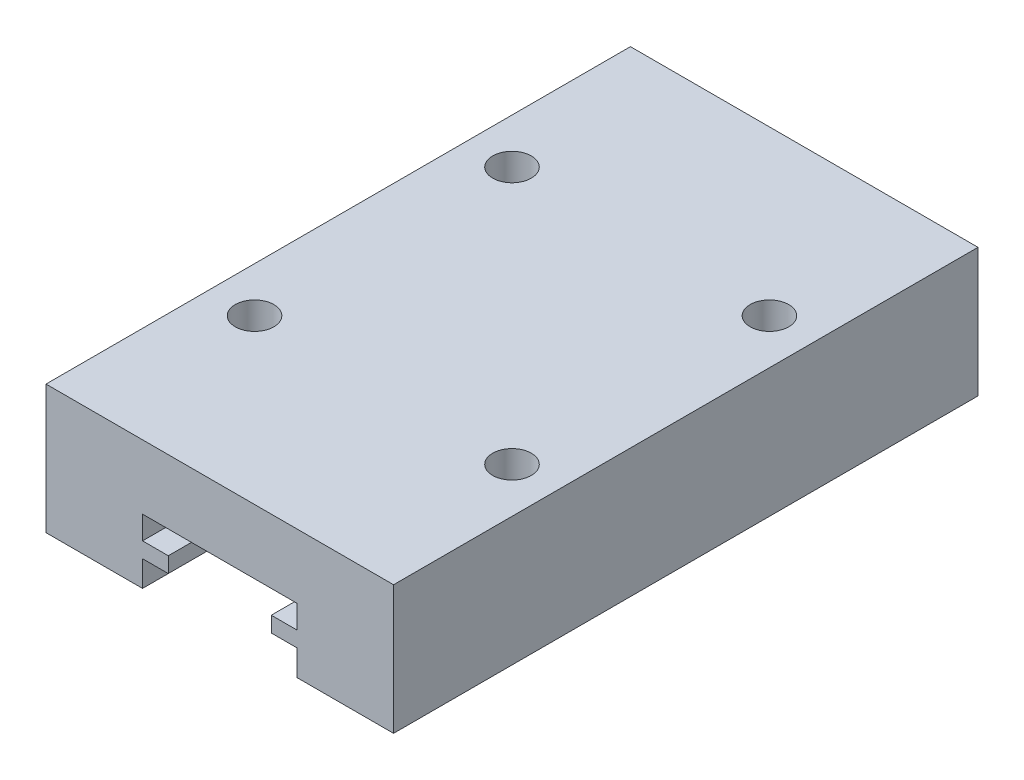
SolidWorks part; units mm, degrees
ref_plane "Plan de face" through (0, 0, 0) normal (0, 0, 1) x (1, 0, 0)
ref_plane "Plan de dessus" through (0, 0, 0) normal (0, 1, 0) x (1, 0, 0)
ref_plane "Plan de droite" through (0, 0, 0) normal (1, 0, 0) x (0, 0, -1)
sketch "Esquisse1" plane through (0, 0, 0) normal (0, 0, 1) x (1, 0, 0)
  line L0 (-22.7955, 10) -> (4.2045, 10)
  line L1 (4.2045, 10) -> (4.2045, 0)
  line L2 (4.2045, 0) -> (-3.2955, 0)
  line L3 (-3.2955, 0) -> (-3.2955, 2)
  line L4 (-3.2955, 2) -> (-5.2955, 2)
  line L5 (-5.2955, 2) -> (-5.2955, 3.2)
  line L6 (-5.2955, 3.2) -> (-3.2955, 3.2)
  line L7 (-3.2955, 3.2) -> (-3.2955, 5)
  line L8 (-3.2955, 5) -> (-15.2955, 5)
  line L9 (-15.2955, 5) -> (-15.2955, 3.2)
  line L10 (-15.2955, 3.2) -> (-13.2955, 3.2)
  line L11 (-13.2955, 3.2) -> (-13.2955, 2)
  line L12 (-13.2955, 2) -> (-15.2955, 2)
  line L13 (-15.2955, 2) -> (-15.2955, 0)
  line L14 (-15.2955, 0) -> (-22.7955, 0)
  line L15 (-22.7955, 0) -> (-22.7955, 10)
  point P15 (0, 0)
  dimension "D1" = 1.2
  dimension "D2" = 2
  dimension "D3" = 1.8
  dimension "D4" = 2
  dimension "D5" = 10
  dimension "D6" = 7.5
  dimension "D7" = 27
extrude "Boss.-Extru.1" add sketch "Esquisse1" along normal blind 45.4
sketch "Esquisse2" plane through (0, 10, 0) normal (0, 1, 0) x (1, 0, 0)
  line L0 (-19.2955, -32.7) -> (0.7045, -32.7) construction
  line L1 (0.7045, -32.7) -> (0.7045, -12.7) construction
  line L2 (4.2045, -45.4) -> (-22.7955, -45.4) construction
  line L3 (4.2045, -45.4) -> (4.2045, 0) construction
  circle A0 centre (-19.2955, -32.7) radius 1.5
  circle A1 centre (-19.2955, -12.7) radius 1.5
  circle A2 centre (0.7045, -12.7) radius 1.5
  circle A3 centre (0.7045, -32.7) radius 1.5
  point P8 (-9.2955, -32.7)
  point P11 (-9.2955, -45.4)
  point P12 (0.7045, -22.7)
  point P15 (4.2045, -22.7)
  dimension "D3" = 3
  dimension "D1" = 20
  dimension "D2" = 20
extrude "Enlèv. mat.-Extru.1" cut sketch "Esquisse2" against normal blind 3.5
